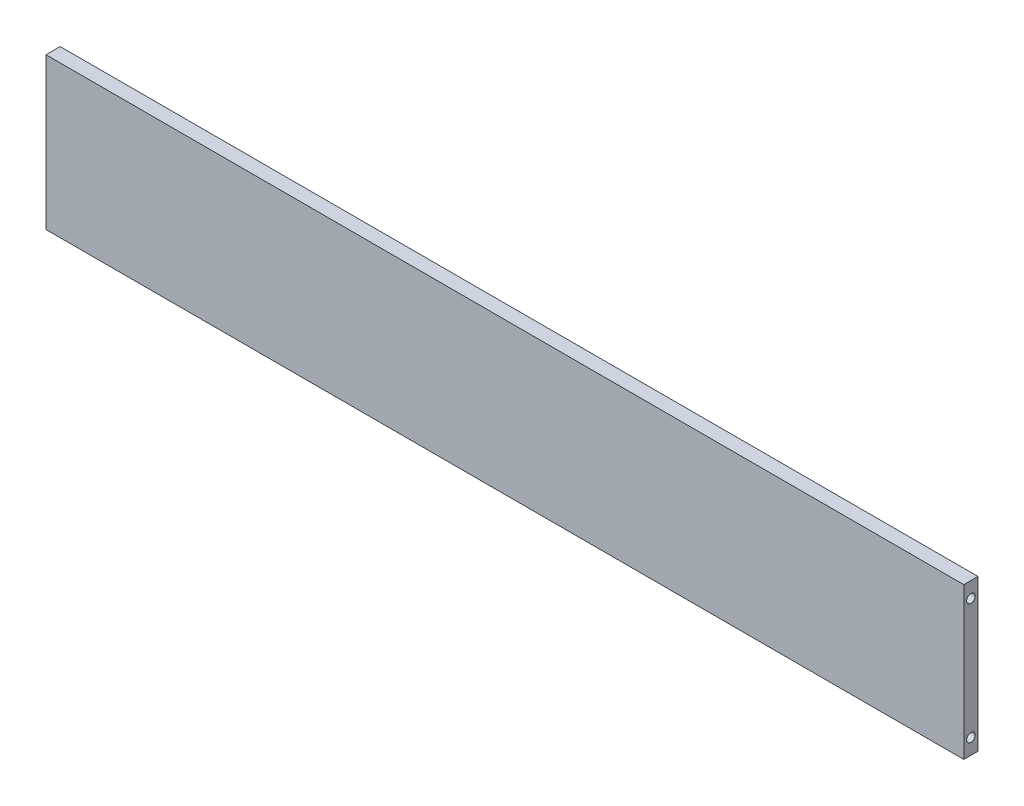
SolidWorks part; units mm, degrees
ref_plane "Front Plane" through (0, 0, 0) normal (0, 0, 1) x (1, 0, 0)
ref_plane "Top Plane" through (0, 0, 0) normal (0, 1, 0) x (1, 0, 0)
ref_plane "Right Plane" through (0, 0, 0) normal (1, 0, 0) x (0, 0, -1)
sketch "Sketch1" plane through (0, 0, 0) normal (0, 0, 1) x (1, 0, 0)
  line L1 (194, 32) -> (-194, 32)
  line L2 (194, 32) -> (194, -32)
  line L3 (194, -32) -> (-194, -32)
  line L4 (-194, 32) -> (-194, -32)
  line L5 (194, 32) -> (-194, -32) construction
  line L6 (194, -32) -> (-194, 32) construction
  point P0 (0, 0)
  dimension "D1" = 388
  dimension "D2" = 64
extrude "Boss-Extrude1" add sketch "Sketch1" along normal blind 6
sketch "Sketch2" plane through (-194, 0, 0) normal (-1, 0, 0) x (0, 0, 1)
  line L0 (0, 0) -> (6, 0) construction
  line L1 (6, 32) -> (6, -32) construction
  circle A0 centre (3, 25.445) radius 1.8
  circle A1 centre (3, -25.445) radius 1.8
  dimension "D1" = 25.445
extrude "Cut-Extrude1" cut sketch "Sketch2" against normal up to next
